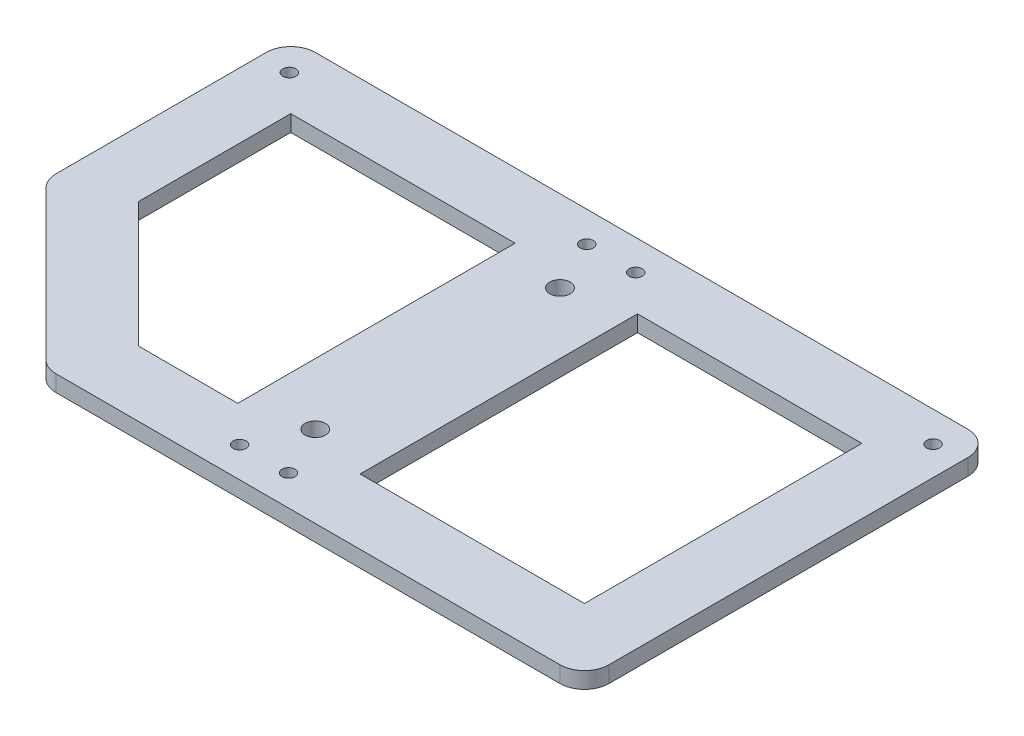
SolidWorks part; units mm, degrees
ref_plane "Ebene vorne" through (0, 0, 0) normal (0, 0, 1) x (1, 0, 0)
ref_plane "Ebene oben" through (0, 0, 0) normal (0, 1, 0) x (1, 0, 0)
ref_plane "Ebene rechts" through (0, 0, 0) normal (1, 0, 0) x (0, 0, -1)
sketch "Skizze1" plane through (0, 0, 0) normal (0, 1, 0) x (1, 0, 0)
  line L0 (-43, -25) -> (43, 25) construction
  line L1 (-43, 25) -> (43, 25)
  line L2 (-43, 25) -> (-43, -25)
  line L3 (-43, -25) -> (43, -25)
  line L4 (43, 25) -> (43, -25)
  point P5 (0, 0)
  dimension "D1" = 50
  dimension "D2" = 86
extrude "Aufsatz-Linear austragen1" add sketch "Skizze1" along normal blind 2
hole_wizard "Ø1.6 (1.6) Diameter Hole1" positions "Skizze2" profile "Skizze3" hole size "Ø1.6" standard "ANSI Metric" end condition through all
sketch "Skizze2" plane through (0, 2, 0) normal (0, 1, 0) x (1, 0, 0)
  line L1 (-39.45, 21.275) -> (-3, 21.275)
  line L2 (-39.45, 21.275) -> (-39.45, -21.275)
  line L3 (-39.45, -21.275) -> (-3, -21.275)
  line L4 (-3, 21.275) -> (-3, -21.275)
  point P0 (-39.45, 21.275)
  point P2 (-3, 21.275)
  point P4 (-3, -21.275)
  point P81 (-3, 0)
  dimension "D1" = 42.55
  dimension "D2" = 36.45
  dimension "D3" = 3
sketch "Skizze3" plane through (-39.45, 2, -21.275) normal (1, 0, 0) x (0, 0, 1)
  line L0 (0, 0) -> (0, 2)
  line L1 (0, 2) -> (0.8, 2)
  line L2 (0.8, 2) -> (0.8, 0)
  line L5 (0.8, 0) -> (0, 0)
  line L11 (0, -6.35) -> (0, 107.95) construction
  dimension "Thru Hole Dia." = 1.6
  dimension "Thru Hole Depth" = 2
mirror "Spiegeln1" about plane through (0, 0, 0) normal (1, 0, 0) of "Ø1.6 (1.6) Diameter Hole1"
hole_wizard "M3x0.5 Gewindebohrung1" positions "Skizze4" profile "Skizze5" tap size "M3x0.5" standard "ANSI Metrisch"
sketch "Skizze4" plane through (0, 2, 0) normal (0, 1, 0) x (1, 0, 0)
  line L0 (0, 15) -> (0, -15)
  point P0 (0, 15)
  point P2 (0, -15)
  point P8 (0, 0)
  dimension "D1" = 30
sketch "Skizze5" plane through (0, 2, -15) normal (1, 0, 0) x (0, 0, 1)
  line L0 (0, 0) -> (0, 9.2511)
  line L1 (0, 9.2511) -> (1.25, 8.5)
  line L2 (1.25, 8.5) -> (1.25, 0)
  line L5 (1.25, 0) -> (0, 0)
  line L10 (0, 9.2511) -> (-1.25, 8.5) construction
  line L11 (0, -6.35) -> (0, 107.95) construction
  dimension "Bohrerdurchmesser" = 2.5
  dimension "Bohrungstiefe" = 8.5
  dimension "Spitzenwinkel" = 118
sketch "Skizze6" plane through (0, 0, 0) normal (0, 1, 0) x (1, 0, 0)
  line L0 (43, 25) -> (-43, 25) construction
  line L1 (-7.5, -17) -> (-35, -17)
  line L2 (-7.5, -17) -> (-7.5, 17)
  line L3 (-7.5, 17) -> (-35, 17)
  line L4 (-35, -17) -> (-35, 17)
  line L5 (7.5, 17) -> (35, 17)
  line L6 (7.5, 17) -> (7.5, -17)
  line L7 (7.5, -17) -> (35, -17)
  line L8 (35, 17) -> (35, -17)
  line L9 (43, -25) -> (43, 25) construction
  line L10 (-43, -25) -> (43, -25) construction
  line L11 (-43, 25) -> (-43, -25) construction
  circle A0 centre (0, -15) radius 1.25 construction
  dimension "D6" = 7.5
  dimension "D1" = 7.5
  dimension "D2" = 8
  dimension "D3" = 8
  dimension "D4" = 8
  dimension "D5" = 8
  dimension "D7" = 8
  dimension "D8" = 8
extrude "Schnitt-Linear austragen1" cut sketch "Skizze6" along normal through all
fillet "Fillet1" radius 3 4 edges at (-43, 1, -25) (43, 1, -25) (43, 1, 25) (-43, 1, 25)
sketch "Sketch1" plane through (0, 2, 0) normal (0, 1, 0) x (1, 0, 0)
  line L0 (-43, 22) -> (-43, -22) construction
  line L1 (-43, -5) -> (-23, -5)
  line L2 (-43, -5) -> (-43, -25)
  line L3 (-43, -25) -> (-23, -25)
  line L4 (-23, -5) -> (-23, -25)
  line L5 (-40, -25) -> (40, -25) construction
  dimension "D1" = 20
  dimension "D2" = 20
extrude "Cut-Extrude1" cut sketch "Sketch1" against normal up to next
sketch "Sketch2" plane through (0, 2, 0) normal (0, 1, 0) x (1, 0, 0)
  line L0 (-43, -5) -> (-23, -25)
  line L2 (-19.6863, -17) -> (-35, -1.6863)
  line L4 (-35, 17) -> (-35, -5) construction
  line L5 (-23, -17) -> (-7.5, -17) construction
  line L6 (-43, -5) -> (-35, -5)
  line L7 (-35, -5) -> (-35, -1.6863)
  line L8 (-19.6863, -17) -> (-23, -17)
  line L9 (-23, -17) -> (-23, -25)
  dimension "D1" = 8
extrude "Boss-Extrude1" add sketch "Sketch2" against normal up to surface (2 mm away) up to face at (21.25, 0, 0)
fillet "Fillet2" radius 3 2 edges at (-43, 1, 5) (-23, 1, 25)
